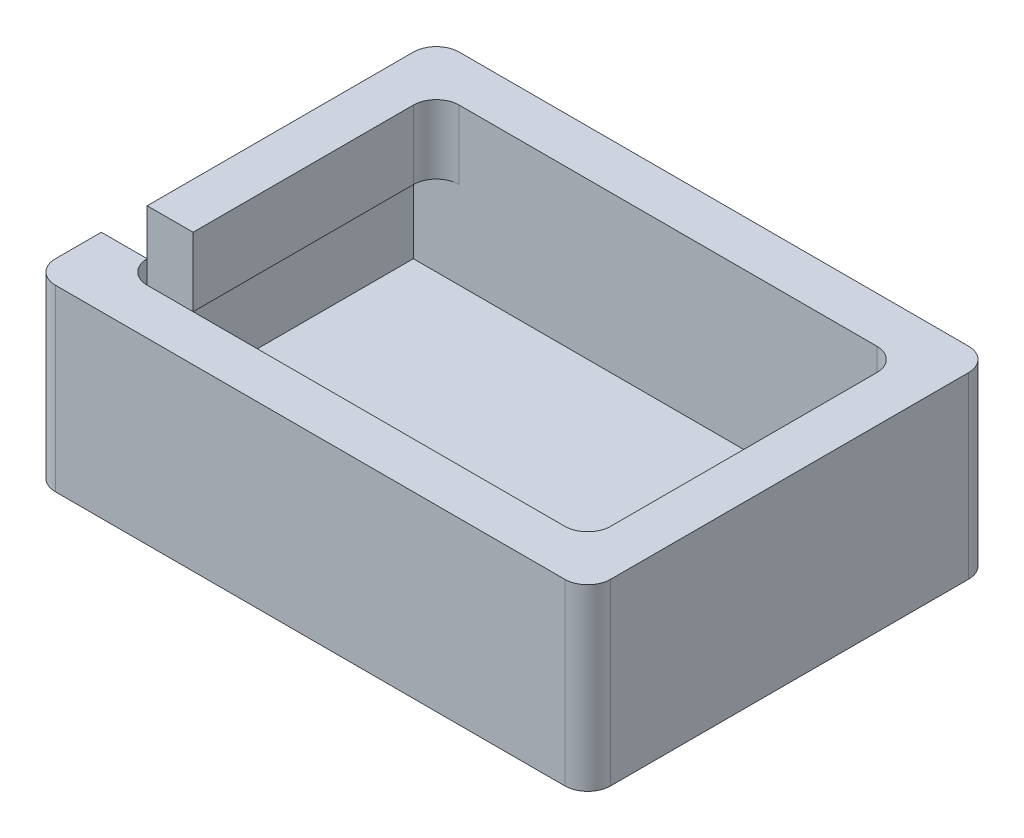
SolidWorks part; units mm, degrees
ref_plane "Alzado" through (0, 0, 0) normal (0, 0, 1) x (1, 0, 0)
ref_plane "Planta" through (0, 0, 0) normal (0, 1, 0) x (1, 0, 0)
ref_plane "Vista lateral" through (0, 0, 0) normal (1, 0, 0) x (0, 0, -1)
sketch "Croquis1" plane through (0, 0, 0) normal (0, 1, 0) x (1, 0, 0)
  line L0 (-60.5, 44) -> (-60.5, -44)
  line L1 (-50.5, 34) -> (50.5, 34)
  line L2 (-50.5, 34) -> (-50.5, -34)
  line L3 (-50.5, -34) -> (50.5, -34)
  line L4 (50.5, 34) -> (50.5, -34)
  line L5 (-60.5, -44) -> (60.5, -44)
  line L6 (60.5, 44) -> (60.5, -44)
  line L7 (-60.5, 44) -> (60.5, 44)
  point P4 (0, -34)
  point P6 (-50.5, 0)
  dimension "D1" = 68
  dimension "D2" = 101
  dimension "D3" = 10
extrude "Saliente-Extruir1" add sketch "Croquis1" along normal blind 15
sketch "Croquis2" plane through (0, 0, 0) normal (0, 1, 0) x (1, 0, 0)
  line L1 (-55.5, 34) -> (55.5, 34)
  line L2 (-55.5, 34) -> (-55.5, -34)
  line L3 (-55.5, -34) -> (55.5, -34)
  line L4 (55.5, 34) -> (55.5, -34)
  line L8 (60.5, 44) -> (-60.5, 44)
  line L9 (-60.5, 44) -> (-60.5, -44)
  line L10 (-60.5, -44) -> (60.5, -44)
  line L11 (60.5, -44) -> (60.5, 44)
  line L12 (60.5, 44) -> (-60.5, 44)
  line L13 (-60.5, 44) -> (-60.5, -44)
  line L14 (-60.5, -44) -> (60.5, -44)
  line L15 (60.5, -44) -> (60.5, 44)
  point P4 (0, -34)
  point P6 (-55.5, 0)
  dimension "D1" = 111
  dimension "D2" = 68
  dimension "D3" = 0
extrude "Saliente-Extruir2" add sketch "Croquis2" against normal blind 19
fillet "Redondeo1" radius 5 4 edges at (50.5, 7.5, 34) (50.5, 7.5, -34) (-50.5, 7.5, -34) (-50.5, 7.5, 34)
fillet "Redondeo2" radius 5 4 edges at (-60.5, -2, 44) (-60.5, -2, -44) (60.5, -2, -44) (60.5, -2, 44)
sketch "Croquis3" plane through (0, 0, 0) normal (1, 0, 0) x (0, 0, -1)
  line L0 (39, 15) -> (-39, 15) construction
  line L1 (-19, 15) -> (-29, 15)
  line L2 (-19, 15) -> (-19, 0)
  line L3 (-19, 0) -> (-29, 0)
  line L4 (-29, 15) -> (-29, 0)
  line L6 (-29, 0) -> (29, 0) construction
  point P6 (-27.9006, 0)
  point P10 (0, 0)
  point P11 (0, 0)
  point P13 (0, 0)
  dimension "D1" = 10
extrude "Cortar-Extruir1" cut sketch "Croquis3" against normal through all
sketch "Croquis4" plane through (0, -19, 0) normal (0, -1, 0) x (1, 0, 0)
  line L4 (55.5, 44) -> (-55.5, 44)
  line L5 (-60.5, 39) -> (-60.5, -39)
  line L6 (-55.5, -44) -> (55.5, -44)
  line L7 (60.5, -39) -> (60.5, 39)
  line L8 (55.5, 44) -> (-55.5, 44)
  line L9 (-60.5, 39) -> (-60.5, -39)
  line L10 (-55.5, -44) -> (55.5, -44)
  line L11 (60.5, -39) -> (60.5, 39)
  arc A4 (-55.5, 44) -> (-60.5, 39) centre (-55.5, 39) ccw
  arc A5 (-60.5, -39) -> (-55.5, -44) centre (-55.5, -39) ccw
  arc A6 (55.5, -44) -> (60.5, -39) centre (55.5, -39) ccw
  arc A7 (60.5, 39) -> (55.5, 44) centre (55.5, 39) ccw
  arc A8 (-55.5, 44) -> (-60.5, 39) centre (-55.5, 39) ccw
  arc A9 (-60.5, -39) -> (-55.5, -44) centre (-55.5, -39) ccw
  arc A10 (55.5, -44) -> (60.5, -39) centre (55.5, -39) ccw
  arc A11 (60.5, 39) -> (55.5, 44) centre (55.5, 39) ccw
  dimension "D1" = 0
extrude "Saliente-Extruir3" add sketch "Croquis4" along normal blind 5
